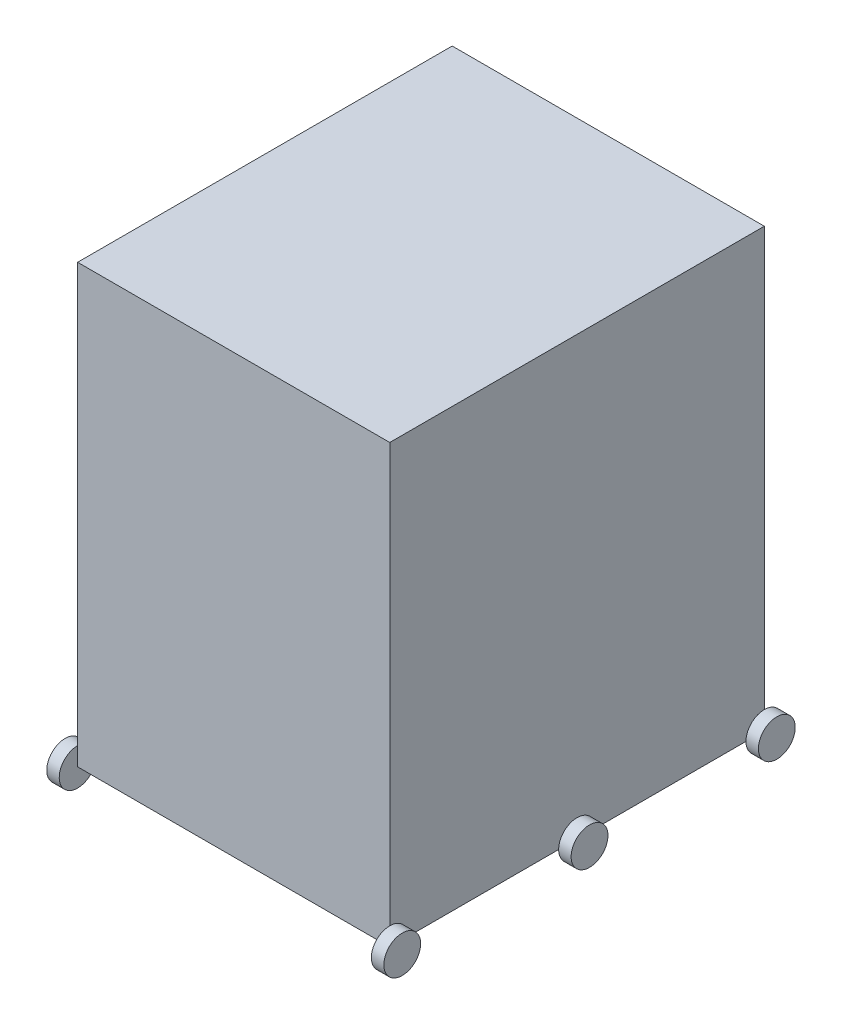
SolidWorks part; units mm, degrees
material "Maple"
ref_plane "Front Plane" through (0, 0, 0) normal (0, 0, 1) x (1, 0, 0)
ref_plane "Top Plane" through (0, 0, 0) normal (0, 1, 0) x (1, 0, 0)
ref_plane "Right Plane" through (0, 0, 0) normal (1, 0, 0) x (0, 0, -1)
sketch "Sketch1" plane through (0, 0, 0) normal (0, 1, 0) x (1, 0, 0)
  line L1 (-154.4444, -75.1576) -> (95.5556, -75.1576)
  line L2 (-154.4444, -75.1576) -> (-154.4444, 224.8424)
  line L3 (-154.4444, 224.8424) -> (95.5556, 224.8424)
  line L4 (95.5556, -75.1576) -> (95.5556, 224.8424)
  dimension "D1" = 250
  dimension "D2" = 300
extrude "Boss-Extrude1" add sketch "Sketch1" along normal blind 350
sketch "Sketch2" plane through (95.5556, 0, 0) normal (1, 0, 0) x (0, 0, -1)
  line L0 (-75.1576, 0) -> (224.8424, 0) construction
  circle A0 centre (-75.1576, 0) radius 14.75
  circle A1 centre (224.8424, 0) radius 14.75
  circle A2 centre (74.8424, 0) radius 14.75
  dimension "D1" = 29.5
  dimension "D2" = 29.5
  dimension "D3" = 29.5
extrude "Boss-Extrude2" add sketch "Sketch2" along normal blind 10
pattern_linear "LPattern2" count 2 spacing 260 along (-1, 0, 0) of "Boss-Extrude2"
